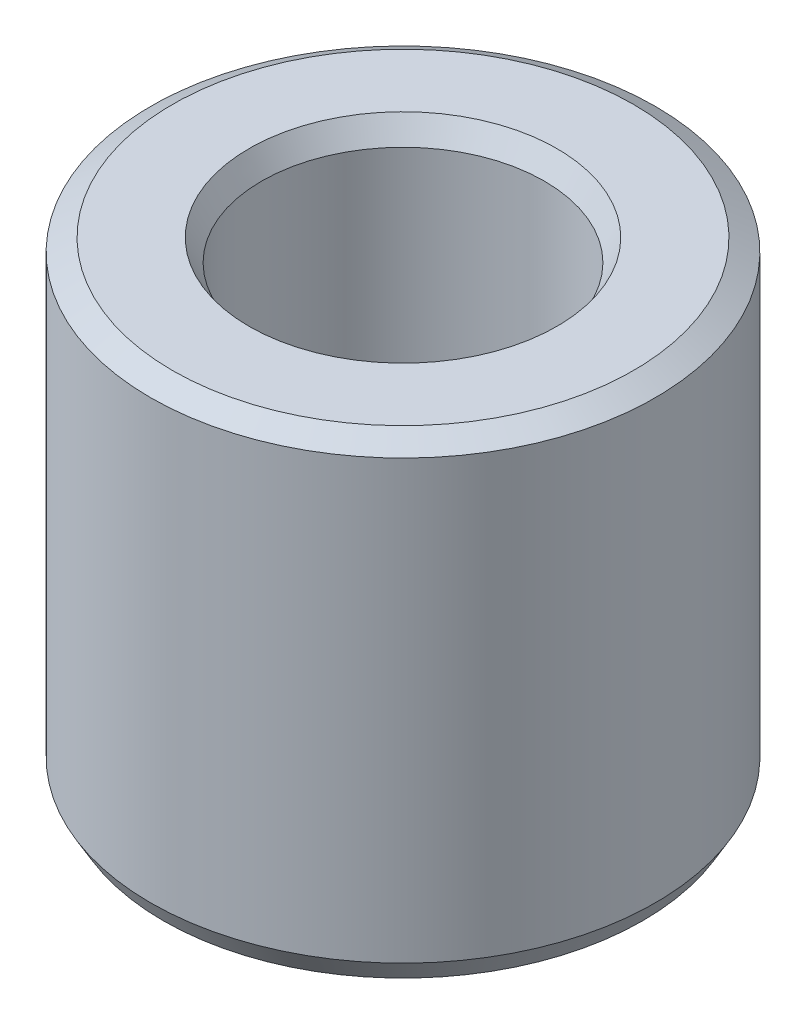
SolidWorks part; units mm, degrees
ref_plane "Front Plane" through (0, 0, 0) normal (0, 0, 1) x (1, 0, 0)
ref_plane "Top Plane" through (0, 0, 0) normal (0, 1, 0) x (1, 0, 0)
ref_plane "Right Plane" through (0, 0, 0) normal (1, 0, 0) x (0, 0, -1)
sketch "Sketch1" plane through (0, 0, 0) normal (0, 1, 0) x (1, 0, 0)
  circle A0 centre (0, 0) radius 7.5
  dimension "SLEEVE_OD" = 15
extrude "Boss-Extrude1" add sketch "Sketch1" along normal blind 14.025
sketch "Sketch2" plane through (0, 0, 0) normal (0, 1, 0) x (1, 0, 0)
  circle A0 centre (0, 0) radius 4.2015
  dimension "BORE_D" = 8.4031
extrude "Cut-Extrude1" cut sketch "Sketch2" along normal through all
chamfer "Chamfer1" distance 0.3749 angle 60 4 edges at (0, 14.025, 4.2015) (0, 0, 4.2015) (0, 0, 7.5) (0, 14.025, 7.5) first distance on face at (0, 14.025, 4.2015) first distance on face at (0, 0, 4.2015) first distance on face at (0, 14.025, 7.5)
